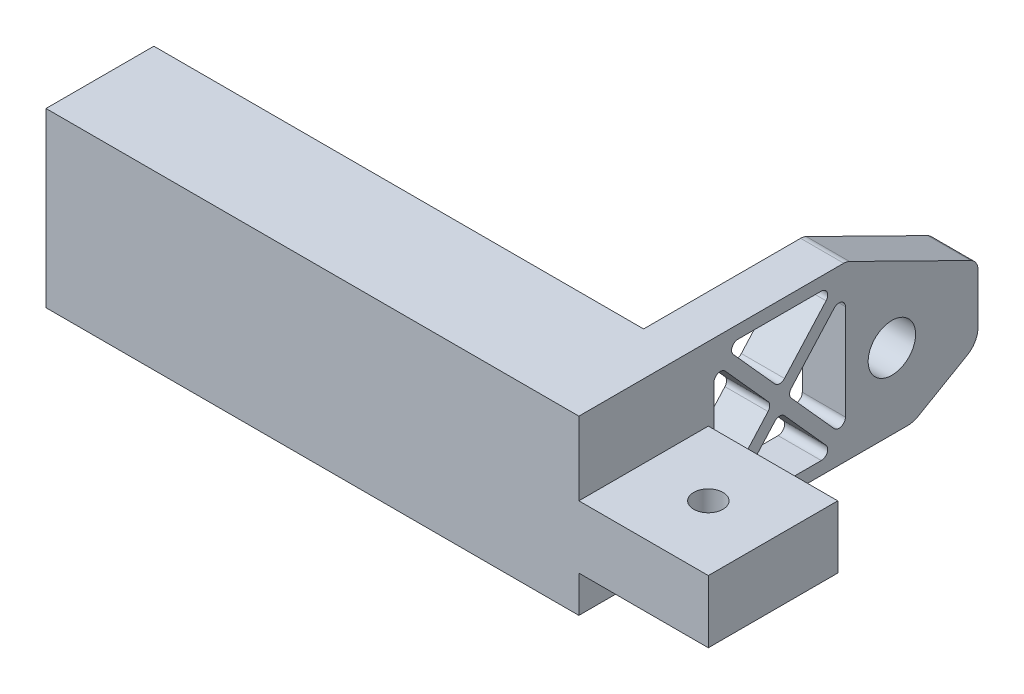
SolidWorks part; units mm, degrees
material "PLA"
ref_plane "Front Plane" through (0, 0, 0) normal (0, 0, 1) x (1, 0, 0)
ref_plane "Top Plane" through (0, 0, 0) normal (0, 1, 0) x (1, 0, 0)
ref_plane "Right Plane" through (0, 0, 0) normal (1, 0, 0) x (0, 0, -1)
sketch "Sketch1" plane through (0, 0, 0) normal (1, 0, 0) x (0, 0, -1)
  line L1 (-35.9146, 20.1296) -> (56.5854, 20.1296)
  line L2 (-35.9146, 20.1296) -> (-35.9146, -19.8704)
  line L3 (-35.9146, -19.8704) -> (56.5854, -19.8704)
  line L4 (56.5854, 20.1296) -> (56.5854, -19.8704)
  dimension "D1" = 92.5
  dimension "D2" = 40
extrude "Boss-Extrude1" add sketch "Sketch1" along normal blind 10
sketch "Sketch4" plane through (0, 0, 0) normal (-1, 0, 0) x (0, 0, 1)
  line L11 (-56.5854, 20.1296) -> (35.9146, 20.1296) construction
  line L12 (10.9146, 20.1296) -> (35.9146, 20.1296)
  line L13 (10.9146, 20.1296) -> (10.9146, -19.8704)
  line L14 (10.9146, -19.8704) -> (35.9146, -19.8704)
  line L15 (35.9146, 20.1296) -> (35.9146, -19.8704)
  line L16 (10.9146, 20.1296) -> (35.9146, -19.8704) construction
  line L17 (10.9146, -19.8704) -> (35.9146, 20.1296) construction
  line L18 (18.2896, 12.7546) -> (18.2896, -12.4954)
  line L19 (18.2896, -12.4954) -> (28.5396, -12.4954)
  line L20 (28.5396, 12.7546) -> (28.5396, -12.4954)
  line L21 (18.2896, 12.7546) -> (28.5396, 12.7546)
  point P4 (23.4146, 0.1296)
  dimension "D1" = 25
  dimension "D2" = 7.375
sketch "Sketch5" plane through (0, 0, 0) normal (-1, 0, 0) x (0, 0, 1)
  line L0 (35.9146, -19.8704) -> (-56.5854, -19.8704) construction
  line L2 (35.9146, 20.1296) -> (35.9146, -19.8704) construction
  circle A0 centre (-36.6254, -2.4304) radius 5.5
  dimension "D1" = 11
  dimension "D2" = 17.44
  dimension "D3" = 72.54
extrude "Cut-Extrude1" cut sketch "Sketch5" against normal blind 27
sketch "Sketch6" plane through (10, 0, 0) normal (1, 0, 0) x (0, 0, -1)
  line L0 (-35.9146, 20.1296) -> (-35.9146, -19.8704) construction
  line L1 (-5.9146, -2.8704) -> (-35.9146, -2.8704)
  line L2 (-5.9146, -2.8704) -> (-5.9146, 3.1296)
  line L3 (-5.9146, 3.1296) -> (-35.9146, 3.1296)
  line L4 (-35.9146, -2.8704) -> (-35.9146, 3.1296)
  line L5 (-5.9146, -2.8704) -> (-35.9146, 3.1296) construction
  line L6 (-5.9146, 3.1296) -> (-35.9146, -2.8704) construction
  line L8 (-35.9146, -19.8704) -> (56.5854, -19.8704) construction
  point P0 (-20.9146, 0.1296)
  dimension "D1" = 30
  dimension "D2" = 6
  dimension "D3" = 20
extrude "Boss-Extrude5" add sketch "Sketch6" along normal blind 30
sketch "Sketch7" plane through (0, -2.8704, 0) normal (0, -1, 0) x (1, 0, 0)
  line L1 (40, 35.9146) -> (10, 35.9146)
  line L2 (40, 35.9146) -> (40, 5.9146)
  line L3 (40, 5.9146) -> (10, 5.9146)
  line L4 (10, 35.9146) -> (10, 5.9146)
extrude "Boss-Extrude6" add sketch "Sketch7" along normal blind 8.5
extrude "Boss-Extrude7" add sketch "Sketch4" along normal blind 113.5
fillet "Fillet1" radius 3 4 edges at (-113.5, -12.4954, 23.4146) (-113.5, 0.1296, 28.5396) (-113.5, 12.7546, 23.4146) (-113.5, 0.1296, 18.2896)
chamfer "Chamfer1" distance 15 angle 63.75 1 edges at (5, 20.1296, -56.5854) first distance on face at (5, 0.1296, -56.5854)
fillet "Fillet3" radius 3 2 edges at (5, 20.1296, -26.1684) (5, 5.1296, -56.5854)
chamfer "Chamfer3" distance 15 angle 30 1 edges at (5, -19.8704, -56.5854) first distance on face at (-34.5, -19.8704, -3.252)
fillet "Fillet7" radius 5 2 edges at (5, -19.8704, -41.5854) (5, -11.2102, -56.5854)
sketch "Sketch9" plane through (10, 0, 0) normal (1, 0, 0) x (0, 0, -1)
  line L6 (25.8575, 15.1296) -> (12.4139, 0.1296)
  line L7 (12.4139, 0.1296) -> (25.8575, -14.8704)
  line L8 (25.8575, -14.8704) -> (25.8575, 0.1296)
  line L9 (25.4689, 20.1296) -> (-35.9146, 20.1296) construction
  line L10 (-4.6146, 17.1296) -> (25.8575, 17.1296)
  line L11 (-4.6146, 17.1296) -> (-4.6146, -16.8704)
  line L12 (-4.6146, -16.8704) -> (25.8575, -16.8704)
  line L13 (25.8575, 17.1296) -> (25.8575, -16.8704)
  line L14 (-35.9146, -19.8704) -> (40.2456, -19.8704) construction
  line L15 (-4.6146, 17.1296) -> (25.8575, -16.8704) construction
  line L16 (25.8575, 17.1296) -> (-4.6146, -16.8704) construction
  line L17 (-4.6146, 0.1296) -> (25.8575, 0.1296) construction
  line L18 (10.6214, 17.1296) -> (10.6214, -16.8704) construction
  line L19 (10.6214, 17.1296) -> (23.6214, 17.1296)
  line L20 (23.6214, 17.1296) -> (10.6214, 2.6245)
  line L21 (10.6214, 2.6245) -> (-2.3786, 17.1296)
  line L22 (-2.3786, 17.1296) -> (10.6214, 17.1296)
  line L23 (-2.3786, 17.1296) -> (23.6214, 17.1296)
  line L24 (25.8575, 0.1296) -> (25.8575, 15.1296)
  line L25 (-5.9146, -11.3704) -> (-5.9146, 3.1296) construction
  line L26 (10.6214, -2.3654) -> (-2.3786, -16.8704)
  line L27 (23.6214, -16.8704) -> (10.6214, -2.3654)
  line L28 (10.6214, -16.8704) -> (23.6214, -16.8704)
  line L29 (-2.3786, -16.8704) -> (10.6214, -16.8704)
  line L30 (-4.6146, -14.8704) -> (-4.6146, 0.1296)
  line L31 (8.829, 0.1296) -> (-4.6146, -14.8704)
  line L32 (-4.6146, 15.1296) -> (8.829, 0.1296)
  line L33 (-4.6146, 0.1296) -> (-4.6146, 15.1296)
  dimension "D1" = 3
  dimension "D2" = 3
  dimension "D3" = 13
  dimension "D4" = 13
  dimension "D5" = 3
  dimension "D6" = 15
  dimension "D7" = 15
  dimension "D8" = 1.3
sketch "Sketch10" plane through (0, 3.1296, 0) normal (0, 1, 0) x (1, 0, 0)
  line L0 (40, -5.9146) -> (10, -35.9146) construction
  line L1 (40, -35.9146) -> (10, -5.9146) construction
  point P10 (25, -20.9146)
hole_wizard "M8 Tapped Hole1" positions "Sketch10" profile "Sketch11" tap size "M8" standard "ISO"
sketch "Sketch11" plane through (25, 3.1296, 20.9146) normal (1, 0, 0) x (0, 0, 1)
  line L0 (0, 0) -> (0, 24.2929)
  line L1 (0, 24.2929) -> (3.4, 22.25)
  line L2 (3.4, 22.25) -> (3.4, 0)
  line L5 (3.4, 0) -> (0, 0)
  line L10 (0, 24.2929) -> (-3.4, 22.25) construction
  line L11 (0, -6.35) -> (0, 107.95) construction
  dimension "Tap Drill Dia." = 6.8
  dimension "Tap Drill Depth" = 22.25
  dimension "Drill Angle" = 118
cosmetic thread "Hole Thread1" parameters "D1"=16, "D2"=8
extrude "Cut-Extrude2" cut sketch "Sketch9" against normal through all contours L22 L19 L20 L21 | L24 L6 L7 L8 | L26 L29 L28 L27 | L30 L33 L32 L31
fillet "Fillet8" radius 1.5 12 edges at (5, -14.8704, 4.6146) (5, 15.1296, 4.6146) (5, 0.1296, -8.829) (5, -16.8704, 2.3786) (5, -16.8704, -23.6214) (5, -2.3654, -10.6214) (5, -14.8704, -25.8575) (5, 0.1296, -12.4139) (5, 15.1296, -25.8575) (5, 2.6245, -10.6214) (5, 17.1296, -23.6214) (5, 17.1296, 2.3786)
